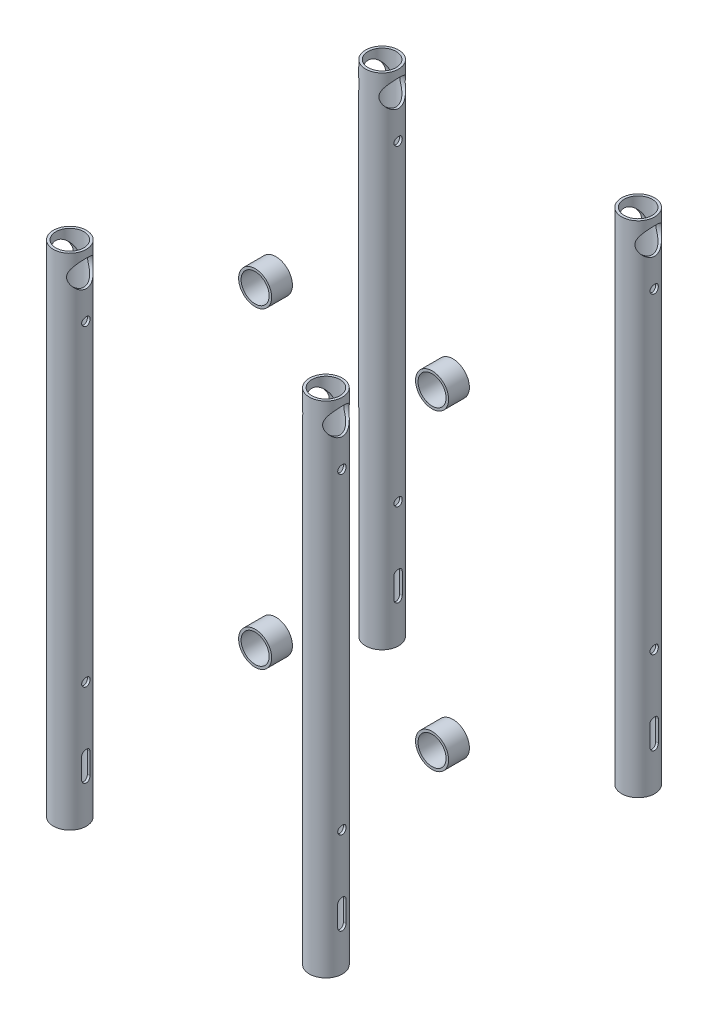
SolidWorks part; units mm, degrees
ref_plane "Front Plane" through (0, 0, 0) normal (0, 0, 1) x (1, 0, 0)
ref_plane "Top Plane" through (0, 0, 0) normal (0, 1, 0) x (1, 0, 0)
ref_plane "Right Plane" through (0, 0, 0) normal (1, 0, 0) x (0, 0, -1)
sketch "Sketch1" plane through (0, 0, 0) normal (0, 1, 0) x (1, 0, 0)
  line L1 (-123, 150) -> (123, 150) construction
  line L2 (-123, 150) -> (-123, -150) construction
  line L3 (-123, -150) -> (123, -150) construction
  line L4 (123, 150) -> (123, -150) construction
  line L5 (-123, 150) -> (123, -150) construction
  line L6 (-123, -150) -> (123, 150) construction
  line L7 (-138.875, 165.875) -> (138.875, 165.875) construction
  line L8 (-138.875, 165.875) -> (-138.875, -165.875) construction
  line L9 (-138.875, -165.875) -> (138.875, -165.875) construction
  line L10 (138.875, 165.875) -> (138.875, -165.875) construction
  circle A0 centre (-123, 150) radius 15.875
  circle A1 centre (-123, 150) radius 13.462
  circle A2 centre (123, 150) radius 15.875
  circle A3 centre (123, 150) radius 13.462
  circle A4 centre (123, -150) radius 15.875
  circle A5 centre (-123, -150) radius 13.462
  circle A6 centre (-123, -150) radius 15.875
  circle A7 centre (123, -150) radius 13.462
  point P0 (0, 0)
  dimension "D1" = 31.75
  dimension "D2" = 2.413
  dimension "D3" = 246
  dimension "D4" = 300
  dimension "D5" = 277.75
  dimension "D6" = 331.75
extrude "Boss-Extrude1" add sketch "Sketch1" against normal blind 450 and the other way blind 30
sketch "Sketch3" plane through (0, 0, 0) normal (1, 0, 0) x (0, 0, -1)
  line L0 (0, 0) -> (0, -30) construction
  line L1 (0, -30) -> (0, -400) construction
  line L2 (-150, -30) -> (150, -30) construction
  line L3 (-150, -400) -> (150, -400) construction
  line L4 (-150, -30) -> (-150, -400) construction
  line L5 (150, -30) -> (150, -400) construction
  line L6 (-150, -410) -> (-150, -390) construction
  line L7 (-154, -410) -> (-154, -390)
  line L8 (-146, -410) -> (-146, -390)
  line L9 (150, -410) -> (150, -390) construction
  line L10 (146, -410) -> (146, -390)
  line L11 (154, -410) -> (154, -390)
  line L12 (-150, 30) -> (-150, -450) construction
  line L13 (-134.125, 30) -> (-165.875, 30) construction
  line L14 (-165.875, -450) -> (-134.125, -450) construction
  line L15 (-150, -450) -> (150, -450) construction
  line L16 (134.125, -450) -> (165.875, -450) construction
  line L17 (150, -450) -> (150, 30) construction
  line L18 (163.462, 30) -> (136.538, 30) construction
  line L19 (150, 30) -> (-150, 30) construction
  line L20 (-150, -330) -> (150, -330) construction
  line L21 (-150, 10) -> (150, 10) construction
  line L22 (0, 0) -> (-150, 0) construction
  circle A0 centre (-150, -30) radius 4
  circle A1 centre (150, -30) radius 4
  arc A2 (-154, -410) -> (-146, -410) centre (-150, -410) ccw
  arc A3 (-146, -390) -> (-154, -390) centre (-150, -390) ccw
  arc A4 (146, -410) -> (154, -410) centre (150, -410) ccw
  arc A5 (154, -390) -> (146, -390) centre (150, -390) ccw
  circle A6 centre (-150, -330) radius 4
  circle A7 centre (150, -330) radius 4
  circle A9 centre (-150, 10) radius 12.7
  circle A10 centre (150, 10) radius 12.7
  circle A11 centre (-150, -30) radius 25 construction
  point P13 (-150, -400)
  point P20 (150, -400)
  dimension "D1" = 8
  dimension "D2" = 8
  dimension "D7" = 300
  dimension "D8" = 30
  dimension "D9" = 25.4
  dimension "D10" = 50
  dimension "D3" = 20
  dimension "D4" = 60
  dimension "D5" = 30
  dimension "D6" = 360
  dimension "D11" = 20
  dimension "D12" = 40
extrude "Cut-Extrude1" cut sketch "Sketch3" against normal blind 350 and the other way blind 350
sketch "Sketch4" plane through (0, 0, 0) normal (0, 0, 1) x (1, 0, 0)
  line L0 (-85, -30) -> (85, -30) construction
  line L1 (-85, -60.875) -> (-85, -45) construction
  line L2 (0, 0) -> (0, -30) construction
  line L3 (-85, -60.875) -> (85, -60.875) construction
  line L4 (85, -60.875) -> (85, -30) construction
  line L5 (0, 0) -> (-123, 0) construction
  line L7 (-123, 0) -> (-123, -60.875) construction
  line L8 (-123, -60.875) -> (-85, -60.875) construction
  line L9 (-85, -45) -> (-85, -30) construction
  line L10 (-85, -30) -> (-85, 0) construction
  line L11 (-85, -60.875) -> (-85, -360.875) construction
  line L12 (-85, -360.875) -> (85, -360.875) construction
  line L13 (85, -360.875) -> (85, -60.875) construction
  line L14 (0, -60.875) -> (0, -30) construction
  line L15 (-123, 30) -> (-123, 0) construction
  line L16 (-107.125, 30) -> (-138.875, 30) construction
  circle A3 centre (-85, -60.875) radius 15.875
  circle A4 centre (-85, -60.875) radius 13.462
  circle A5 centre (85, -60.875) radius 15.875
  circle A6 centre (85, -60.875) radius 13.462
  circle A7 centre (-85, -360.875) radius 15.875
  circle A8 centre (-85, -360.875) radius 13.462
  circle A9 centre (85, -360.875) radius 13.462
  circle A10 centre (85, -360.875) radius 15.875
  dimension "D1" = 170
  dimension "D2" = 15
  dimension "D3" = 31.75
  dimension "D4" = 2.413
  dimension "D6" = 300
  dimension "D7" = 30
  dimension "D8" = 15.875
extrude "Boss-Extrude2" add sketch "Sketch4" along normal blind 10 and the other way blind 10 separate body
